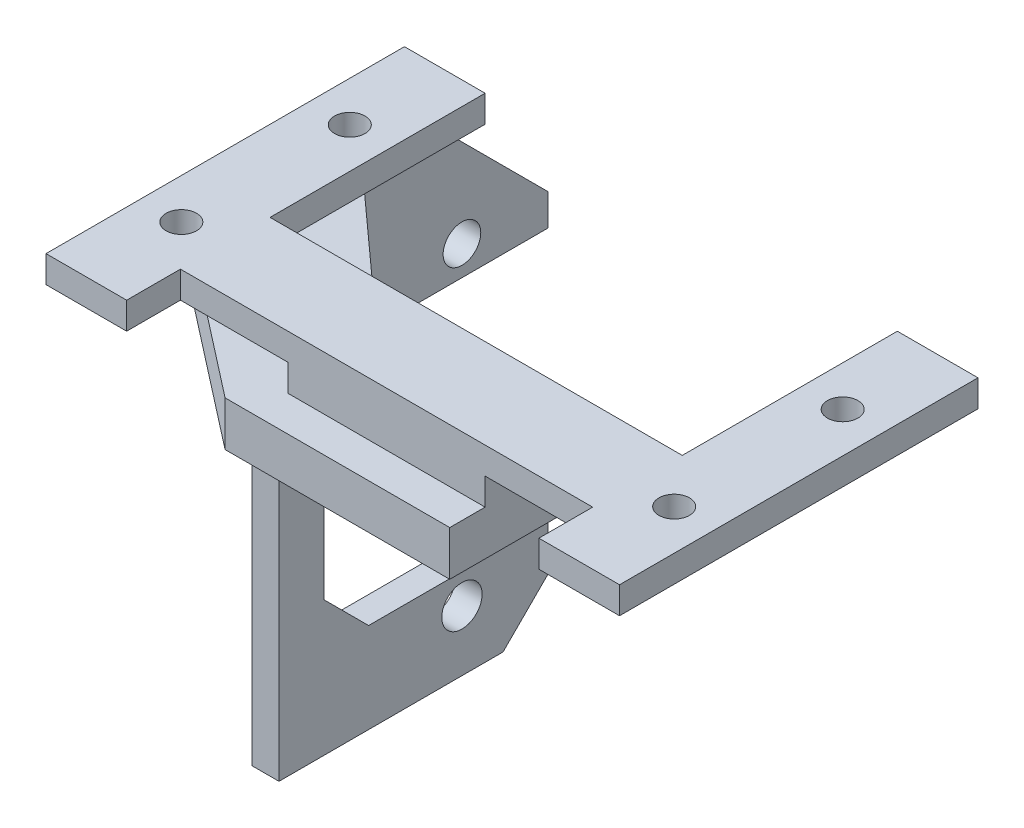
SolidWorks part; units mm, degrees
ref_plane "前视基准面" through (0, 0, 0) normal (0, 0, 1) x (1, 0, 0)
ref_plane "上视基准面" through (0, 0, 0) normal (0, 1, 0) x (1, 0, 0)
ref_plane "右视基准面" through (0, 0, 0) normal (1, 0, 0) x (0, 0, -1)
sketch "草图1" plane through (0, 0, 0) normal (0, 1, 0) x (1, 0, 0)
  line L0 (0, -55) -> (0, 55) construction
  line L1 (-55, 0) -> (55, 0) construction
  line L2 (32, -20) -> (23, -20)
  line L3 (-32, -20) -> (-23, -20)
  line L4 (-32, -20) -> (-32, 20)
  line L5 (-32, 20) -> (-23, 20)
  line L6 (-23, -20) -> (-23, 20)
  line L7 (-32, -20) -> (-23, 20) construction
  line L8 (-32, 20) -> (-23, -20) construction
  line L9 (23, -20) -> (23, 20)
  line L10 (32, -20) -> (32, 20)
  line L11 (32, 20) -> (23, 20)
  circle A0 centre (-27.5, 9.4) radius 1.7
  circle A1 centre (27.5, 9.4) radius 1.7
  circle A2 centre (27.5, -9.4) radius 1.7
  circle A3 centre (-27.5, -9.4) radius 1.7
  point P12 (-27.5, 0)
  dimension "D1" = 3.4
  dimension "D2" = 18.8
  dimension "D3" = 55
  dimension "D4" = 9
  dimension "D5" = 40
extrude "凸台-拉伸1" add sketch "草图1" along normal blind 3
sketch "草图2" plane through (0, 0, 0) normal (0, -1, 0) x (-1, 0, 0)
  line L0 (-23, 20) -> (-23, -20) construction
  line L1 (23, -14) -> (-23, -14)
  line L2 (23, -14) -> (23, -4)
  line L3 (23, -4) -> (-23, -4)
  line L4 (-23, -14) -> (-23, -4)
  line L5 (23, -14) -> (-23, -4) construction
  line L6 (23, -4) -> (-23, -14) construction
  point P0 (0, -9)
  dimension "D1" = 10
  dimension "D2" = 9
extrude "凸台-拉伸2" add sketch "草图2" against normal blind 3
sketch "草图3" plane through (0, 0, 0) normal (0, -1, 0) x (1, 0, 0)
  line L0 (-23, 4) -> (23, 4) construction
  line L1 (-11, 4) -> (11, 4)
  line L2 (-11, 4) -> (-11, 14)
  line L3 (-11, 14) -> (11, 14)
  line L4 (11, 4) -> (11, 14)
  line L5 (-11, 4) -> (11, 14) construction
  line L6 (-11, 14) -> (11, 4) construction
  line L7 (23, 14) -> (-23, 14) construction
  point P0 (0, 9)
  dimension "D1" = 22
extrude "凸台-拉伸3" add sketch "草图3" along normal blind 8
sketch "草图10" plane through (0, -8, 0) normal (0, -1, 0) x (1, 0, 0)
  line L0 (-11, 14) -> (-29, 0)
  line L1 (-11, 4) -> (-11, 14)
  line L2 (-11, 4) -> (-29, -12.2664)
  line L3 (-29, -12.2664) -> (-29, 0)
  dimension "D1" = 18
extrude "凸台-拉伸5" add sketch "草图10" against normal blind 5
sketch "草图11" plane through (-29, 0, 0) normal (-1, 0, 0) x (0, 0, 1)
  line L0 (0, -3) -> (0, -8) construction
  line L1 (0, -3) -> (-30, -3)
  line L2 (0, -3) -> (0, -55)
  line L3 (0, -55) -> (-30, -55)
  line L4 (-30, -3) -> (-30, -55)
  line L6 (0, -3) -> (-12.2664, -3) construction
  dimension "D1" = 30
  dimension "D2" = 52
extrude "凸台-拉伸6" add sketch "草图11" against normal blind 3
sketch "草图12" plane through (-26, 0, 0) normal (1, 0, 0) x (0, 0, -1)
  circle A0 centre (20.414, -13.24) radius 2.1
  circle A1 centre (20.414, -48.24) radius 2.25
extrude "切除-拉伸3" cut sketch "草图12" against normal blind 13
sketch "草图13" plane through (-29, 0, 0) normal (-1, 0, 0) x (0, 0, 1)
  line L0 (-30, -3) -> (-30, -55) construction
  line L1 (-30, -16.54) -> (-5, -16.54)
  line L2 (-30, -16.54) -> (-30, -44.94)
  line L3 (-30, -44.94) -> (-5, -44.94)
  line L4 (-5, -16.54) -> (-5, -44.94)
  circle A0 centre (-20.414, -13.24) radius 2.1 construction
  circle A1 centre (-20.414, -48.24) radius 2.25 construction
  dimension "D1" = 3.3
  dimension "D2" = 3.3
  dimension "D3" = 25
extrude "切除-拉伸4" cut sketch "草图13" against normal blind 13
chamfer "倒角3" distance 10 angle 45 1 edges at (-27.5, -3, -30)
chamfer "倒角4" distance 5 angle 45 1 edges at (-27.5, -55, -30)
chamfer "倒角5" distance 5 angle 45 2 edges at (-27.5, -16.54, -5) (-27.5, -44.94, -5)
sketch "草图14" plane through (-10.9308, 0, 14.0538) normal (-0.6139, 0, 0.7894) x (0.7894, 0, 0.6139)
  line L1 (-22.8912, -3) -> (-0.0877, -3)
  line L2 (-22.8912, -3) -> (-22.8912, -8)
  line L3 (-22.8912, -8) -> (-0.0877, -8)
  line L4 (-0.0877, -3) -> (-0.0877, -8)
extrude "凸台-拉伸7" add sketch "草图14" along normal blind 5
sketch "草图15" plane through (11, 0, 0) normal (1, 0, 0) x (0, 0, -1)
  line L1 (-17.9468, -3) -> (-14, -3)
  line L2 (-17.9468, -3) -> (-17.9468, -8)
  line L3 (-17.9468, -8) -> (-14, -8)
  line L4 (-14, -3) -> (-14, -8)
extrude "凸台-拉伸8" add sketch "草图15" against normal up to body
chamfer "倒角6" distance 5 1 edges at (-29, -5.5, 0)
sketch "草图17" plane through (0, -8, 0) normal (0, -1, 0) x (1, 0, 0)
  line L0 (-29, 0) -> (-20.3259, 10.2869)
  line L1 (-20.3259, 10.2869) -> (-17.3383, 7.7676)
  line L2 (-17.3383, 7.7676) -> (-26, -4.1557)
  line L3 (-26, 0) -> (-26, -9.5553) construction
  line L4 (-26, -4.1557) -> (-29, 0)
extrude "凸台-拉伸9" add sketch "草图17" along normal blind 5
